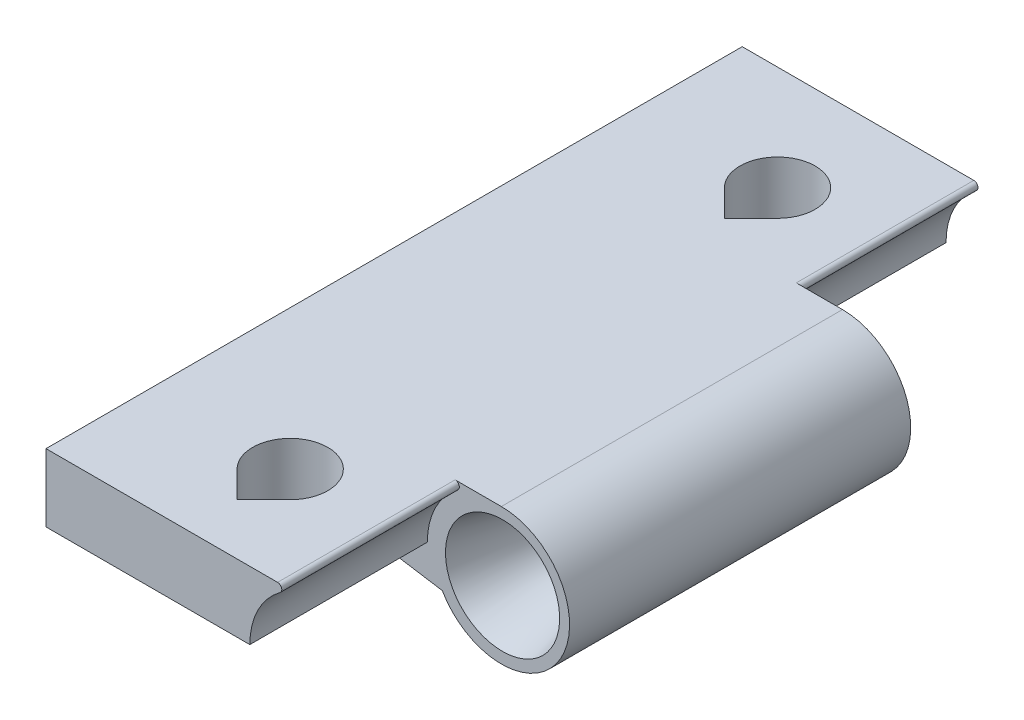
SolidWorks part; units mm, degrees
ref_plane "Front Plane" through (0, 0, 0) normal (0, 0, 1) x (1, 0, 0)
ref_plane "Top Plane" through (0, 0, 0) normal (0, 1, 0) x (1, 0, 0)
ref_plane "Right Plane" through (0, 0, 0) normal (1, 0, 0) x (0, 0, -1)
ref_plane "Plane1" through (0, 0, -25) normal (0, 0, -1) x (-1, 0, 0)
sketch "Sketch1" plane through (0, 0, -25) normal (0, 0, -1) x (-1, 0, 0)
  line L0 (5.4, 0) -> (20.0381, 0)
  line L1 (20.0381, 0) -> (20.0381, 4.8713)
  line L2 (20.0381, 4.8713) -> (3.4048, 4.8713)
  arc A0 (3.4048, 4.8713) -> (3.2256, 4.3307) centre (3.4048, 4.5713) ccw
  arc A1 (3.2256, 4.3307) -> (5.4, 0) centre (0, 0) cw
  dimension "D1" = 5.4
  dimension "D3" = 0.3
  dimension "D2" = 4.8713
extrude "Boss-Extrude1" add sketch "Sketch1" against normal blind 12.75
sketch "Sketch2" plane through (0, 0, -12.25) normal (0, 0, 1) x (1, 0, 0)
  line L0 (-20.0381, 4.8713) -> (-0.0866, 4.8713)
  line L1 (-4.3301, -2.4787) -> (-20.0381, 0.0213)
  line L2 (-20.0381, 0.0213) -> (-20.0381, 4.8713)
  line L3 (-20.0381, 4.8713) -> (-3.4048, 4.8713) construction
  line L4 (-20.0381, 0) -> (-20.0381, 4.8713) construction
  arc A0 (-0.0866, 4.8713) -> (-4.3301, -2.4787) centre (-0.0866, -0.0287) cw
  dimension "D1" = 4.9
extrude "Boss-Extrude2" add sketch "Sketch2" along normal blind 24.5
sketch "Sketch3" plane through (0, 0, 12.25) normal (0, 0, 1) x (1, 0, 0)
  line L0 (-20.0381, 4.8713) -> (-3.4048, 4.8713)
  line L1 (-5.4, 0) -> (-20.0381, 0)
  line L2 (-20.0381, 0) -> (-20.0381, 4.8713)
  line L3 (-0.0866, 4.8713) -> (-20.0381, 4.8713) construction
  line L4 (-20.0381, 4.8713) -> (-20.0381, 0.0213) construction
  line L5 (-5.4, 0) -> (-20.0381, 0) construction
  arc A0 (-3.4048, 4.8713) -> (-3.2256, 4.3307) centre (-3.4048, 4.5713) cw
  arc A1 (-3.2256, 4.3307) -> (-5.4, 0) centre (0, 0) ccw
  dimension "D1" = 5.4
  dimension "D2" = 0.3
extrude "Boss-Extrude3" add sketch "Sketch3" along normal blind 12.75
sketch "Sketch4" plane through (0, 4.8713, 0) normal (0, 1, 0) x (-1, 0, 0)
  line L0 (10, -13.6816) -> (8.0908, -15.5908)
  line L1 (11.9092, -15.5908) -> (10, -13.6816)
  arc A0 (8.0908, -15.5908) -> (11.9092, -15.5908) centre (10, -17.5) ccw
extrude "Cut-Extrude1" cut sketch "Sketch4" against normal through all
sketch "Sketch5" plane through (0, 4.8713, 0) normal (0, 1, 0) x (-1, 0, 0)
  line L0 (10, 21.3184) -> (8.0908, 19.4092)
  line L1 (11.9092, 19.4092) -> (10, 21.3184)
  arc A0 (8.0908, 19.4092) -> (11.9092, 19.4092) centre (10, 17.5) ccw
extrude "Cut-Extrude2" cut sketch "Sketch5" against normal through all
ref_plane "Plane2" through (0, 0, 0) normal (0, -1, 0) x (1, 0, 0)
sketch "Sketch6" plane through (0, 0, 0) normal (0, -1, 0) x (1, 0, 0)
  line L0 (4.1, 12.25) -> (0, 12.25)
  line L1 (0, 12.25) -> (0, -12.25)
  line L2 (0, -12.25) -> (4.1829, -12.25)
  line L3 (0, 12.25) -> (0, -12.25) construction
  arc A0 (4.1829, -12.25) -> (4.1, 12.25) centre (43.0208, 0.1316) cw
  dimension "D1" = 4.1
revolve "Cut-Revolve1" cut sketch "Sketch6" angle 360 about L3 reverse direction yes
fillet "Fillet2" [suppressed] radius 0.25 tangent propagation no
